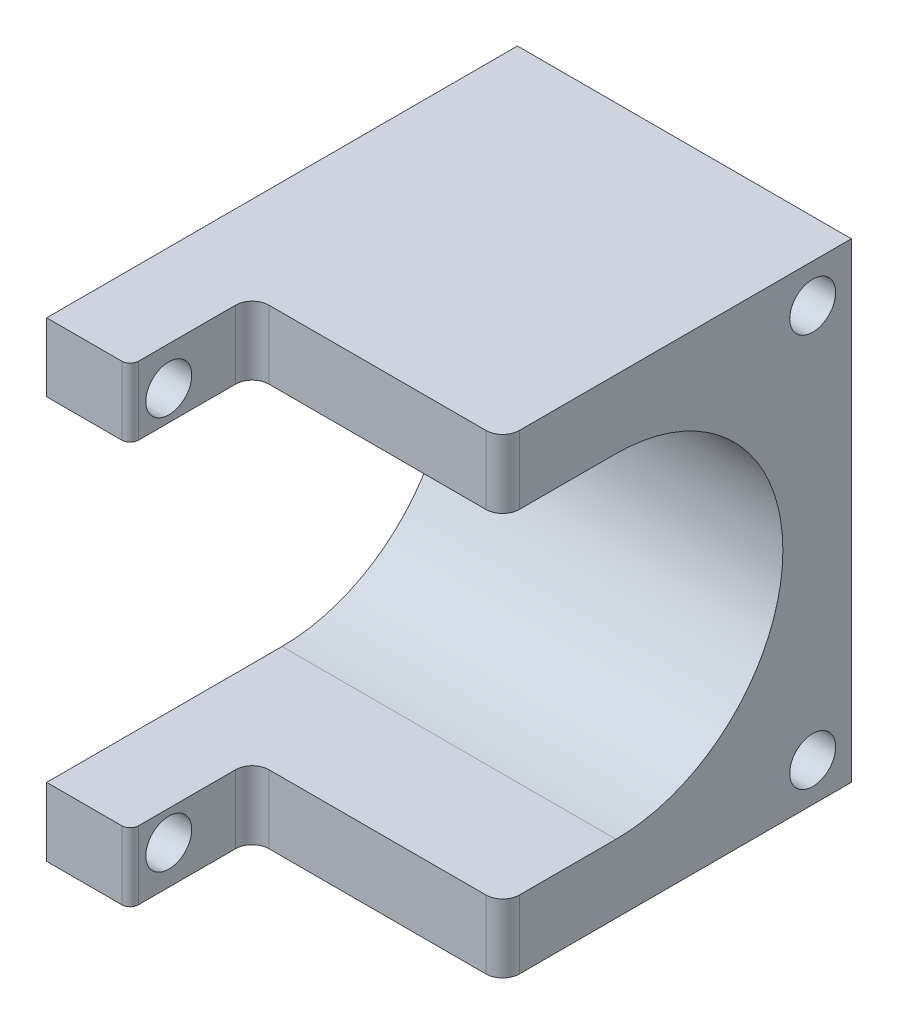
SolidWorks part; units mm, degrees
ref_plane "Front Plane" through (0, 0, 0) normal (0, 0, 1) x (1, 0, 0)
ref_plane "Top Plane" through (0, 0, 0) normal (0, 1, 0) x (1, 0, 0)
ref_plane "Right Plane" through (0, 0, 0) normal (1, 0, 0) x (0, 0, -1)
sketch "Sketch1" plane through (0, 0, 0) normal (1, 0, 0) x (0, 0, -1)
  line L1 (-17.4229, 1.4968) -> (38.9771, 1.4968)
  line L2 (-17.4229, 1.4968) -> (-17.4229, -54.9032)
  line L3 (-17.4229, -54.9032) -> (38.9771, -54.9032)
  line L4 (38.9771, 1.4968) -> (38.9771, -54.9032)
  dimension "D1" = 56.4
  dimension "D2" = 56.4
extrude "Boss-Extrude1" add sketch "Sketch1" along normal blind 40
sketch "Sketch2" plane through (40, 0, 0) normal (1, 0, 0) x (0, 0, -1)
  line L0 (10.7771, 1.4968) -> (10.7771, -54.9032) construction
  line L1 (38.9771, 1.4968) -> (-17.4229, 1.4968) construction
  line L2 (-17.4229, -54.9032) -> (38.9771, -54.9032) construction
  line L3 (-17.4229, -26.7032) -> (38.9771, -26.7032) construction
  line L4 (-17.4229, 1.4968) -> (-17.4229, -54.9032) construction
  line L5 (38.9771, -54.9032) -> (38.9771, 1.4968) construction
  circle A0 centre (-12.7929, -3.1332) radius 2.75
  circle A1 centre (-12.7929, -50.2732) radius 2.75
  circle A2 centre (34.3471, -3.1332) radius 2.75
  circle A3 centre (34.3471, -50.2732) radius 2.75
  dimension "D1" = 5.5
  dimension "D3" = 47.14
  dimension "D2" = 47.14
extrude "Cut-Extrude1" cut sketch "Sketch2" against normal through all
sketch "Sketch3" plane through (40, 0, 0) normal (1, 0, 0) x (0, 0, -1)
  line L0 (-17.4229, 1.4968) -> (-17.4229, -54.9032) construction
  line L1 (-17.4229, -8.1332) -> (29.3471, -8.1332)
  line L2 (-17.4229, -8.1332) -> (-17.4229, -45.2732)
  line L3 (-17.4229, -45.2732) -> (29.3471, -45.2732)
  line L4 (29.3471, -8.1332) -> (29.3471, -45.2732)
  line L5 (38.9771, -54.9032) -> (38.9771, 1.4968) construction
  circle A0 centre (-12.7929, -3.1332) radius 2.75 construction
  circle A1 centre (34.3471, -3.1332) radius 2.75 construction
  point P6 (29.3471, -26.7032)
  point P9 (38.9771, -26.7032)
  dimension "D1" = 5
  dimension "D2" = 5
extrude "Cut-Extrude2" [suppressed] cut sketch "Sketch3" against normal through all
sketch "Sketch4" plane through (40, 0, 0) normal (1, 0, 0) x (0, 0, -1)
  line L0 (38.9771, 1.4968) -> (-17.4229, 1.4968) construction
  line L1 (38.9771, -54.9032) -> (38.9771, 1.4968) construction
  line L2 (10.7771, -6.7032) -> (-17.4229, -6.7032)
  line L3 (-17.4229, 1.4968) -> (-17.4229, -54.9032) construction
  line L4 (10.7771, -46.7032) -> (-17.4229, -46.7032)
  line L5 (-17.4229, -46.7032) -> (-17.4229, -6.7032)
  arc A0 (10.7771, -46.7032) -> (10.7771, -6.7032) centre (10.7771, -26.7032) ccw
  point P5 (10.7771, 1.4968)
  point P9 (38.9771, -26.7032)
  dimension "D1" = 40
extrude "Cut-Extrude3" cut sketch "Sketch4" against normal through all
sketch "Sketch5" plane through (40, 0, 0) normal (1, 0, 0) x (0, 0, -1)
  line L0 (38.9771, 1.4968) -> (-17.4229, 1.4968) construction
  line L1 (-17.4229, -6.7032) -> (-2.7929, -6.7032)
  line L2 (-17.4229, -6.7032) -> (-17.4229, 1.4968)
  line L3 (-17.4229, 1.4968) -> (-2.7929, 1.4968)
  line L4 (-2.7929, -6.7032) -> (-2.7929, 1.4968)
  line L5 (38.9771, -26.7032) -> (30.7771, -26.7032) construction
  line L6 (38.9771, -54.9032) -> (38.9771, 1.4968) construction
  line L7 (-17.4229, -54.9032) -> (-2.7929, -54.9032)
  line L8 (-2.7929, -46.7032) -> (-2.7929, -54.9032)
  line L9 (-17.4229, -46.7032) -> (-2.7929, -46.7032)
  line L10 (-17.4229, -46.7032) -> (-17.4229, -54.9032)
  circle A2 centre (-12.7929, -3.1332) radius 2.75 construction
  arc A3 (10.7771, -46.7032) -> (10.7771, -6.7032) centre (10.7771, -26.7032) ccw construction
  point P7 (-12.7929, -3.1332)
  dimension "D1" = 10
extrude "Cut-Extrude4" cut sketch "Sketch5" against normal offset from surface (30 mm away) 10 up to face at (0, -50.2732, 15.5429)
fillet "Fillet1" radius 2 2 edges at (10, -50.8032, 2.7929) (10, -2.6032, 2.7929)
fillet "Fillet2" radius 2 2 edges at (40, -50.8032, 2.7929) (40, -2.6032, 2.7929)
fillet "Fillet3" radius 1 2 edges at (10, -50.8032, 17.4229) (10, -2.6032, 17.4229)
